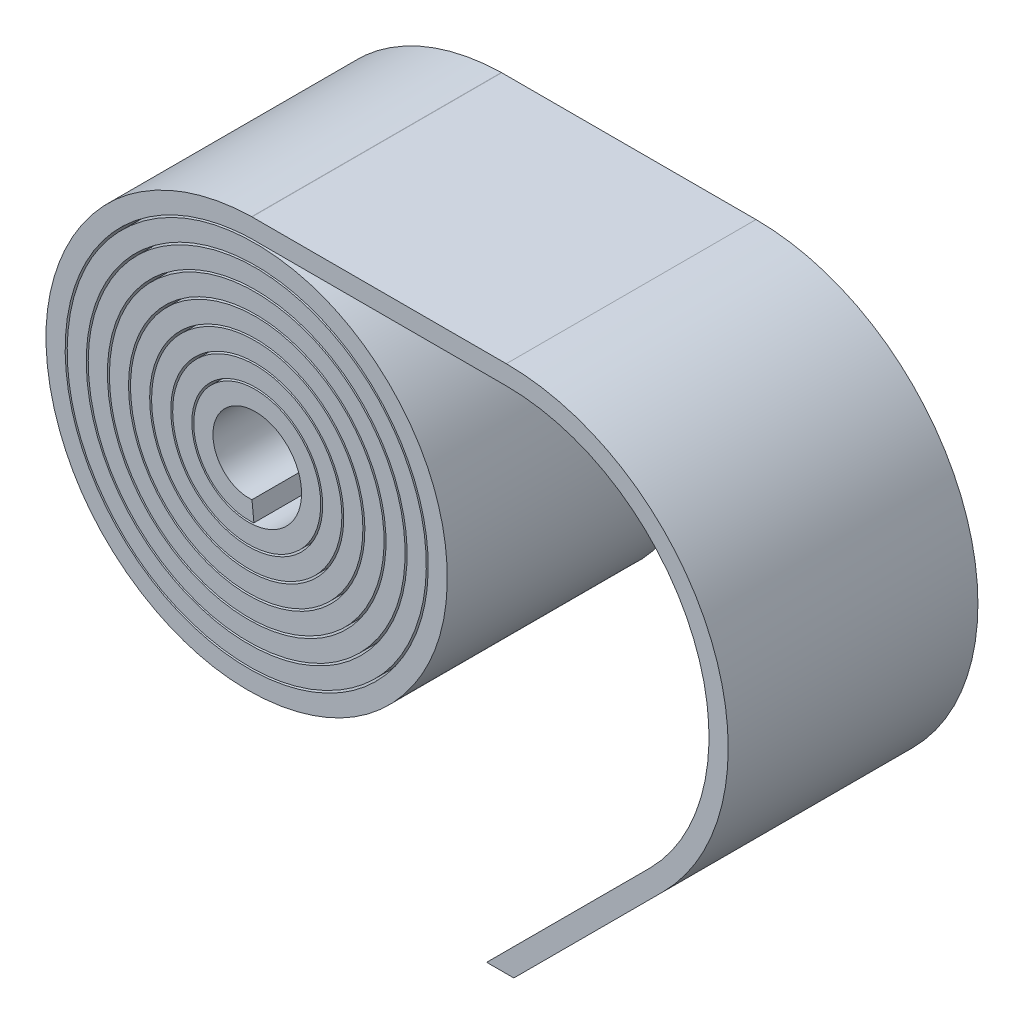
SolidWorks part; units mm, degrees
ref_plane "Front Plane" through (0, 0, 0) normal (0, 0, 1) x (1, 0, 0)
ref_plane "Top Plane" through (0, 0, 0) normal (0, 1, 0) x (1, 0, 0)
ref_plane "Right Plane" through (0, 0, 0) normal (1, 0, 0) x (0, 0, -1)
sketch "Sketch1" plane through (0, 0, 0) normal (0, 0, 1) x (1, 0, 0)
  line L0 (0.3536, 0) -> (-0.3536, 0)
  line L1 (0.3536, 0) -> (4.2426, 3.8891)
  line L4 (4.2426, 3.8891) -> (3.8891, 4.2426)
  line L5 (3.8891, 4.2426) -> (-0.3536, 0)
  point P4 (0, 0)
  dimension "D1" = 45
  dimension "D2" = 0.5
  dimension "D3" = 6
extrude "Boss-Extrude1" add sketch "Sketch1" along normal blind 6.5
sketch "Sketch2" plane through (4.0659, 4.0659, 0) normal (0.7071, 0.7071, 0) x (0, 0, -1)
  line L4 (0, -0.25) -> (0, 0.25)
  line L5 (0, 0.25) -> (-6.5, 0.25)
  line L6 (-6.5, 0.25) -> (-6.5, -0.25)
  line L7 (-6.5, -0.25) -> (0, -0.25)
  line L8 (0, -0.25) -> (0, 0.25)
  line L9 (0, 0.25) -> (-6.5, 0.25)
  line L10 (-6.5, 0.25) -> (-6.5, -0.25)
  line L11 (-6.5, -0.25) -> (0, -0.25)
  dimension "D1" = 0
ref_plane "Plane1" [suppressed] through (6.1872, 6.1872, 0) normal (0.7071, 0.7071, 0) x (0, 0, -1)
sketch "Sketch3" [suppressed] plane through (6.1872, 6.1872, 0) normal (0.7071, 0.7071, 0) x (0, 0, -1)
  line L0 (-6.5, 0.25) -> (-6.5, -0.2731)
  line L1 (0, 0.25) -> (0, -0.2731)
  line L4 (0, -0.25) -> (0, 0.25)
  line L5 (0, 0.25) -> (-6.5, 0.25)
  line L6 (-6.5, 0.25) -> (-6.5, -0.25)
  line L7 (-6.5, -0.25) -> (0, -0.25)
  line L8 (0, -0.25) -> (0, 0.25) construction
  line L9 (0, 0.25) -> (-6.5, 0.25) construction
  line L10 (-6.5, 0.25) -> (-6.5, -0.25) construction
  line L11 (-6.5, -0.25) -> (0, -0.25) construction
  arc A0 (-6.5, 0.25) -> (0, 0.25) centre (-3.25, 10.5625) ccw
  arc A1 (-6.5, -0.2731) -> (0, -0.2731) centre (-3.25, 10.5625) ccw
  arc A2 (-6.6503, -0.2269) -> (0.1503, -0.2269) centre (-3.25, 10.5625) ccw construction
  dimension "D1" = 0
  dimension "D2" = 0.5
loft "Loft1" [suppressed] add profiles "Sketch2", "Sketch3"
sketch "Sketch4" [suppressed] plane through (7.6014, 7.6014, 0) normal (0.7071, 0.7071, 0) x (0, 0, -1)
  line L2 (-6.5, 0.25) -> (-6.5, -0.2731)
  line L3 (0, -0.2731) -> (0, 0.25)
  line L4 (-6.5, 0.25) -> (-6.5, -0.2731)
  line L5 (0, -0.2731) -> (0, 0.25)
  arc A2 (-6.5, 0.25) -> (0, 0.25) centre (-3.25, 10.5625) ccw
  arc A3 (-6.5, -0.2731) -> (0, -0.2731) centre (-3.25, 10.5625) ccw
  arc A4 (-6.5, 0.25) -> (0, 0.25) centre (-3.25, 10.5625) ccw
  arc A5 (-6.5, -0.2731) -> (0, -0.2731) centre (-3.25, 10.5625) ccw
  dimension "D1" = 0
extrude "Boss-Extrude2" [suppressed] add sketch "Sketch4" along normal blind 62
sketch "Sketch5" [suppressed] plane through (7.6014, 7.6014, 0) normal (0.7071, 0.7071, 0) x (0, 0, -1)
  line L2 (-6.5, 0.25) -> (-6.5, -0.2731)
  line L3 (0, -0.2731) -> (0, 0.25)
  line L4 (-6.5, 0.25) -> (-6.5, -0.2731)
  line L5 (0, -0.2731) -> (0, 0.25)
  arc A2 (-6.5, 0.25) -> (0, 0.25) centre (-3.25, 10.5625) ccw
  arc A3 (-6.5, -0.2731) -> (0, -0.2731) centre (-3.25, 10.5625) ccw
  arc A4 (-6.5, 0.25) -> (0, 0.25) centre (-3.25, 10.5625) ccw
  arc A5 (-6.5, -0.2731) -> (0, -0.2731) centre (-3.25, 10.5625) ccw
  dimension "D1" = 0
extrude "Boss-Extrude3" [suppressed] add sketch "Sketch5" along normal blind 28
sketch "Sketch6" [suppressed] plane through (7.6014, 7.6014, 0) normal (0.7071, 0.7071, 0) x (0, 0, -1)
  line L2 (-6.5, 0.25) -> (-6.5, -0.2731)
  line L3 (0, -0.2731) -> (0, 0.25)
  line L4 (-6.5, 0.25) -> (-6.5, -0.2731)
  line L5 (0, -0.2731) -> (0, 0.25)
  arc A2 (-6.5, 0.25) -> (0, 0.25) centre (-3.25, 10.5625) ccw
  arc A3 (-6.5, -0.2731) -> (0, -0.2731) centre (-3.25, 10.5625) ccw
  arc A4 (-6.5, 0.25) -> (0, 0.25) centre (-3.25, 10.5625) ccw
  arc A5 (-6.5, -0.2731) -> (0, -0.2731) centre (-3.25, 10.5625) ccw
  dimension "D1" = 0
extrude "Boss-Extrude4" [suppressed] add sketch "Sketch6" along normal blind 254
sketch "Sketch7" plane through (0, 0, 0) normal (0, 0, 1) x (1, 0, 0)
  line L4 (-6.4619, 13.25) -> (0.1581, 13.25)
  line L5 (0.1581, 13.75) -> (-6.4619, 13.75)
  line L6 (-6.4619, 13.75) -> (-6.4619, 13.25)
  line L7 (3.8891, 4.2426) -> (4.2426, 3.8891)
  circle A0 centre (-6.4619, 8.25) radius 5 construction
  circle A1 centre (-6.4619, 8.25) radius 5 construction
  arc A4 (3.8891, 4.2426) -> (0.1581, 13.25) centre (0.1581, 7.9736) ccw
  arc A5 (4.2426, 3.8891) -> (0.1581, 13.75) centre (0.1581, 7.9736) ccw
  arc A6 (4.2426, 3.8891) -> (0.1581, 13.75) centre (0.1581, 7.9736) ccw construction
  dimension "D2" = 0.5
  dimension "D1" = 0.5
sketch "Sketch8" [suppressed] plane through (0, 0, 0) normal (0, 0, 1) x (1, 0, 0)
  line L4 (-6.4619, 13.25) -> (0.1581, 13.25)
  line L5 (-6.4619, 13.25) -> (-6.4619, 13.75)
  line L6 (-6.4619, 13.75) -> (0.1581, 13.75)
  line L7 (3.8891, 4.2426) -> (4.2426, 3.8891)
  circle A0 centre (-6.4619, 8.25) radius 5 construction
  circle A1 centre (-6.4619, 8.25) radius 5 construction
  arc A4 (3.8891, 4.2426) -> (0.1581, 13.25) centre (0.1581, 7.9736) ccw
  arc A5 (4.2426, 3.8891) -> (0.1581, 13.75) centre (0.1581, 7.9736) ccw
  arc A6 (4.2426, 3.8891) -> (0.1581, 13.75) centre (0.1581, 7.9736) ccw construction
  arc A7 (3.8891, 4.2426) -> (0.1581, 13.25) centre (0.1581, 7.9736) ccw construction
  dimension "D2" = 0.5
  dimension "D1" = 0.5
sketch "Sketch9" [suppressed] plane through (0, 0, 0) normal (0, 0, 1) x (1, 0, 0)
  line L0 (-6.4619, 13.25) -> (0.1581, 13.25)
  line L1 (-6.4619, 13.25) -> (-6.4619, 13.75)
  line L2 (-6.4619, 13.75) -> (0.1581, 13.75)
  line L3 (3.8891, 4.2426) -> (4.2426, 3.8891)
  circle A0 centre (-6.4619, 8.25) radius 5 construction
  circle A1 centre (-6.4619, 8.25) radius 5 construction
  arc A2 (3.8891, 4.2426) -> (0.1581, 13.25) centre (0.1581, 7.9736) ccw
  arc A3 (4.2426, 3.8891) -> (0.1581, 13.75) centre (0.1581, 7.9736) ccw
  arc A4 (4.2426, 3.8891) -> (0.1581, 13.75) centre (0.1581, 7.9736) ccw construction
  arc A5 (3.8891, 4.2426) -> (0.1581, 13.25) centre (0.1581, 7.9736) ccw construction
  dimension "D2" = 0.5
  dimension "D1" = 0.5
extrude "Boss-Extrude7" add sketch "Sketch7" along normal up to surface (6.5 mm away) up to face at (2.0329, 2.0329, 6.5)
extrude "Boss-Extrude8" [suppressed] add sketch "Sketch8" along normal up to surface (6.5 mm away) up to face at (0.2285, 8.0928, 6.5)
extrude "Boss-Extrude9" [suppressed] add sketch "Sketch9" along normal up to surface (6.5 mm away) up to face at (0.2285, 8.0928, 6.5)
sketch "Sketch12" [suppressed] plane through (0, 0, 0) normal (0, 0, 1) x (1, 0, 0)
  circle A0 centre (-6.4619, 8.25) radius 5 construction
  circle A1 centre (-6.4619, 8.25) radius 5
curve "Helix/Spiral1" [suppressed]
sketch "Sketch13" [suppressed] plane through (0, 0, 0) normal (0, 0, 1) x (1, 0, 0)
  line L0 (-6.4707, 13.7499) -> (-6.4619, 13.75)
  line L1 (-6.4619, 13.75) -> (-6.4619, 13.25)
  line L3 (-10.7744, 8.25) -> (-11.2743, 8.2399)
  spline S0 degree 3 poles (-1734.9987, -985.3553) (109.5244, -102.0758) (10.9503, 23.6304) (-9.5072, 12.2267) (-10.113, 11.6566) (-10.9826, 10.3036) (-11.2457, 9.522) (-11.3734, 7.9329) (-11.2381, 7.1267) (-10.607, 5.678) (-10.1119, 5.0367) (-8.8833, 4.0654) (-8.1509, 3.7363) (-6.6233, 3.4616) (-5.8295, 3.5162) (-4.3662, 3.99) (-3.6981, 4.4087) (-2.6409, 5.5064) (-2.2527, 6.1843) (-1.8419, 7.6373) (-1.8195, 8.411) (-2.1394, 9.8723) (-2.4812, 10.5586) (-3.4433, 11.6857) (-4.0625, 12.1255) (-5.4292, 12.6606) (-6.1755, 12.7555) (-7.6191, 12.5845) (-8.3151, 12.3189) (-9.496, 11.4954) (-9.9798, 10.9384) (-19.7569, -8.2721) (108.4322, -92.6781) (765.8503, 1847.6945) knots -1.679483 -1.679483 -1.679483 -1.679483 0.0625 0.0625 0.125 0.125 0.1875 0.1875 0.25 0.25 0.3125 0.3125 0.375 0.375 0.4375 0.4375 0.5 0.5 0.5625 0.5625 0.625 0.625 0.6875 0.6875 0.75 0.75 0.8125 0.8125 0.875 0.875 0.9375 0.9375 2.765017 2.765017 2.765017 2.765017 only from (-6.4619, 13.25) to (-10.7744, 8.25) construction
  spline S1 degree 3 poles (-6.4619, 13.25) (-7.2801, 13.2357) (-8.0901, 13.0167) (-9.5072, 12.2267) (-10.113, 11.6566) (-10.9826, 10.3036) (-11.2457, 9.522) (-11.3734, 7.9329) (-11.2381, 7.1267) (-10.607, 5.678) (-10.1119, 5.0367) (-8.8833, 4.0654) (-8.1509, 3.7363) (-6.6233, 3.4616) (-5.8295, 3.5162) (-4.3662, 3.99) (-3.6981, 4.4087) (-2.6409, 5.5064) (-2.2527, 6.1843) (-1.8419, 7.6373) (-1.8195, 8.411) (-2.1394, 9.8723) (-2.4812, 10.5586) (-3.4433, 11.6857) (-4.0625, 12.1255) (-5.4292, 12.6606) (-6.1755, 12.7555) (-7.6191, 12.5845) (-8.3151, 12.3189) (-9.496, 11.4954) (-9.9798, 10.9384) (-10.6264, 9.6679) (-10.7888, 8.9556) (-10.7744, 8.25) knots 0 0 0 0 0.0625 0.0625 0.125 0.125 0.1875 0.1875 0.25 0.25 0.3125 0.3125 0.375 0.375 0.4375 0.4375 0.5 0.5 0.5625 0.5625 0.625 0.625 0.6875 0.6875 0.75 0.75 0.8125 0.8125 0.875 0.875 0.9375 0.9375 1 1 1 1
  spline S2 degree 1 poles (-6.4707, 13.7499) (-11.2743, 8.2399) knots 0 0 1 1 construction
  spline S3 degree 3 poles (-6.4707, 13.7499) (-7.3581, 13.7344) (-9.1599, 13.2519) (-11.1557, 11.3673) (-12.0281, 8.7814) (-11.5796, 6.112) (-9.9392, 3.9865) (-7.5099, 2.8947) (-4.8746, 3.0758) (-2.6545, 4.4667) (-1.3634, 6.7214) (-1.2888, 9.2966) (-2.4276, 11.5834) (-4.4925, 13.0502) (-6.9836, 13.3674) (-9.3095, 12.4794) (-10.9279, 10.6188) (-11.2902, 9.0229) (-11.2743, 8.2399) knots 0 0 0 0 0.0625 0.125 0.1875 0.25 0.3125 0.375 0.4375 0.5 0.5625 0.625 0.6875 0.75 0.8125 0.875 0.9375 1 1 1 1
  dimension "D1" = 0.5
extrude "Boss-Extrude10" [suppressed] add sketch "Sketch13" along normal up to surface (6.5 mm away) up to face at (0.2285, 8.0928, 6.5)
sketch "Sketch14" [suppressed] plane through (0, 0, 0) normal (0, 0, 1) x (1, 0, 0)
  line L0 (0.1581, 13.25) -> (-6.4619, 13.25) construction
  line L1 (-6.4619, 13.75) -> (-15.4619, 13.75)
  line L2 (-6.4619, 13.75) -> (-6.4619, 13.25)
  line L3 (-6.4619, 13.25) -> (-15.4619, 13.25)
  line L4 (-15.4619, 13.75) -> (-15.4619, 13.25)
  dimension "D1" = 9
extrude "Boss-Extrude11" [suppressed] add sketch "Sketch14" along normal up to surface (6.5 mm away) up to face at (0.2285, 8.0928, 6.5)
sketch "Sketch15" plane through (0, 0, 0) normal (0, 0, 1) x (1, 0, 0)
  circle A0 centre (-6.4619, 8.25) radius 5 construction
  circle A1 centre (-6.4619, 8.25) radius 5
curve "Helix/Spiral2"
sketch "Sketch16" plane through (0, 0, 0) normal (0, 0, 1) x (1, 0, 0)
  line L0 (-6.4707, 13.7499) -> (-6.4619, 13.75)
  line L1 (-6.4619, 13.75) -> (-6.4619, 13.25)
  line L4 (-6.4619, 7.375) -> (-6.4122, 6.8775)
  spline S0 degree 3 poles (-2722.3964, -1245.4042) (118.5986, -153.8828) (15.5928, 22.5679) (-8.8147, 12.6555) (-9.3349, 12.3217) (-10.218, 11.4923) (-10.5808, 10.9969) (-11.1027, 9.9123) (-11.2617, 9.3234) (-11.3575, 8.1315) (-11.2943, 7.5289) (-10.9568, 6.39) (-10.6827, 5.8541) (-9.9627, 4.9193) (-9.517, 4.5207) (-8.5155, 3.9119) (-7.96, 3.7019) (-6.8142, 3.4959) (-6.2244, 3.5) (-5.0891, 3.7188) (-4.544, 3.9334) (-3.5703, 4.5421) (-3.1419, 4.9359) (-2.4574, 5.848) (-2.2014, 6.366) (-1.8932, 7.4557) (-1.8412, 8.0271) (-1.9454, 9.1469) (-2.1015, 9.6948) (-2.5982, 10.6949) (-2.9387, 11.1467) (-3.7564, 11.8955) (-4.2333, 12.1924) (-5.2584, 12.5937) (-5.8062, 12.6981) (-6.8991, 12.7035) (-7.4439, 12.6044) (-8.458, 12.2187) (-8.9272, 11.9322) (-9.7286, 11.2126) (-10.0606, 10.7796) (-10.5456, 9.8267) (-10.6984, 9.3071) (-10.807, 8.2513) (-10.7627, 7.7156) (-10.486, 6.6992) (-10.2536, 6.2189) (-9.6341, 5.3766) (-9.2473, 5.015) (-8.3729, 4.4565) (-7.8855, 4.2599) (-6.8764, 4.0553) (-6.3549, 4.0474) (-5.3476, 4.2185) (-4.862, 4.3975) (-3.9907, 4.9158) (-3.6051, 5.2549) (-2.9837, 6.046) (-2.748, 6.4977) (-2.4554, 7.4518) (-2.3986, 7.9541) (-2.4686, 8.9417) (-2.5954, 9.4268) (-3.013, 10.3159) (-3.3036, 10.7195) (-4.0076, 11.3931) (-4.4207, 11.6629) (-5.3127, 12.0348) (-5.7913, 12.1368) (-6.7494, 12.1624) (-7.2287, 12.0859) (-8.1244, 11.7674) (-8.5405, 11.5255) (-9.2554, 10.911) (-9.5539, 10.5386) (-9.9959, 9.7149) (-10.1391, 9.2638) (-10.2538, 8.3441) (-10.2253, 7.8757) (-10.003, 6.984) (-9.8094, 6.561) (-9.2855, 5.8156) (-8.9555, 5.4935) (-8.2049, 4.9912) (-7.7847, 4.8111) (-6.9113, 4.6145) (-6.4584, 4.598) (-5.5806, 4.7279) (-5.156, 4.8742) (-4.3908, 5.3076) (-4.0504, 5.5945) (-3.4976, 6.2682) (-3.2853, 6.6549) (-3.0147, 7.475) (-2.9564, 7.9082) (-2.9989, 8.7629) (-3.0996, 9.1841) (-3.4438, 9.9588) (-3.6871, 10.3122) (-4.2816, 10.9055) (-4.6326, 11.1452) (-5.3936, 11.4814) (-5.8035, 11.5778) (-6.6266, 11.6169) (-7.0397, 11.5598) (-7.8142, 11.3024) (-8.1754, 11.1022) (-8.7992, 10.5882) (-9.0615, 10.2745) (-9.4544, 9.5772) (-9.5848, 9.1939) (-9.6991, 8.4097) (-9.6829, 8.0091) (-9.5088, 7.2441) (-9.351, 6.88) (-8.9175, 6.2356) (-8.642, 5.9555) (-8.012, 5.515) (-7.6577, 5.3547) (-6.919, 5.1725) (-6.5348, 5.1508) (-5.7879, 5.2459) (-5.4255, 5.3628) (-4.77, 5.7168) (-4.4771, 5.9538) (-3.9982, 6.5142) (-3.8123, 6.8373) (-3.5701, 7.5251) (-3.5137, 7.8895) (-3.5352, 8.6105) (-3.613, 8.9668) (-3.8897, 9.6244) (-4.0884, 9.9254) (-4.5779, 10.4334) (-4.8684, 10.6403) (-5.5009, 10.9346) (-5.8426, 11.022) (-6.5307, 11.0682) (-6.8769, 11.027) (-7.5279, 10.8246) (-7.8325, 10.6633) (-8.3607, 10.2449) (-8.5841, 9.9878) (-8.9221, 9.414) (-9.0365, 9.0974) (-9.1438, 8.4482) (-9.1366, 8.1157) (-9.0043, 7.4791) (-8.8793, 7.1753) (-8.5309, 6.6357) (-8.3076, 6.4002) (-7.7946, 6.0271) (-7.5051, 5.8896) (-6.8997, 5.7285) (-6.5841, 5.7048) (-5.9692, 5.7717) (-5.6701, 5.8622) (-5.1277, 6.1426) (-4.8844, 6.3323) (-4.4847, 6.7833) (-4.3282, 7.0445) (-4.1206, 7.6019) (-4.0695, 7.8979) (-4.0766, 8.4848) (-4.1347, 8.7754) (-4.3499, 9.313) (-4.5068, 9.5597) (-4.8958, 9.9778) (-5.1278, 10.149) (-5.6343, 10.3954) (-5.9085, 10.4704) (-6.4619, 10.517) (-6.7408, 10.4886) (-7.2661, 10.3349) (-7.5124, 10.2096) (-7.9408, 9.8817) (-8.1227, 9.6791) (-8.3999, 9.2255) (-8.4951, 8.9747) (-8.5888, 8.4595) (-8.5873, 8.1952) (-8.4904, 7.6886) (-8.3951, 7.4464) (-8.1263, 7.0155) (-7.9529, 6.8269) (-7.5532, 6.5267) (-7.327, 6.4151) (-6.8535, 6.2813) (-6.6063, 6.2591) (-6.1242, 6.3043) (-5.8895, 6.3716) (-5.4633, 6.584) (-5.2718, 6.7291) (-4.9562, 7.0751) (-4.8321, 7.276) (-4.6653, 7.7052) (-4.6227, 7.9333) (-4.622, 8.3859) (-4.6638, 8.6101) (-4.8236, 9.0251) (-4.9414, 9.2157) (-5.2347, 9.5393) (-5.4101, 9.6722) (-5.7934, 9.8646) (-6.0011, 9.9241) (-6.4201, 9.9646) (-6.6313, 9.9455) (-7.0291, 9.8342) (-7.2155, 9.7419) (-7.54, 9.4993) (-7.6779, 9.349) (-7.8888, 9.0123) (-7.9616, 8.826) (-8.0353, 8.4437) (-8.036, 8.2477) (-7.9681, 7.8724) (-7.8994, 7.6931) (-7.7047, 7.3743) (-7.5786, 7.2349) (-7.2882, 7.0127) (-7.1239, 6.93) (-6.7804, 6.8299) (-6.6013, 6.8126) (-6.2527, 6.8426) (-6.0833, 6.89) (-5.7762, 7.0405) (-5.6386, 7.1435) (-5.4119, 7.3889) (-5.323, 7.5313) (-5.2032, 7.8347) (-5.1725, 7.9957) (-5.1705, 8.314) (-5.1993, 8.4712) (-5.365, 8.9064) (-5.5833, 9.1443) (-6.1095, 9.4096) (-6.4144, 9.4364) (-6.9514, 9.2857) (-7.1811, 9.1098) (-7.459, 8.663) (-7.5065, 8.3947) (-7.4155, 7.9085) (-7.2781, 7.6928) (-0.2208, 2.4009) (69.3767, 103.8125) (-2946.9328, 592.1902) knots -0.321915 -0.321915 -0.321915 -0.321915 0.007812 0.007812 0.015625 0.015625 0.023437 0.023437 0.03125 0.03125 0.039062 0.039062 0.046875 0.046875 0.054687 0.054687 0.0625 0.0625 0.070312 0.070312 0.078125 0.078125 0.085937 0.085937 0.09375 0.09375 0.101562 0.101562 0.109375 0.109375 0.117187 0.117187 0.125 0.125 0.132812 0.132812 0.140625 0.140625 0.148437 0.148437 0.15625 0.15625 0.164062 0.164062 0.171875 0.171875 0.179687 0.179687 0.1875 0.1875 0.195312 0.195312 0.203125 0.203125 0.210938 0.210938 0.21875 0.21875 0.226563 0.226563 0.234375 0.234375 0.242188 0.242188 0.25 0.25 0.257813 0.257813 0.265625 0.265625 0.273438 0.273438 0.28125 0.28125 0.289063 0.289063 0.296875 0.296875 0.304688 0.304688 0.3125 0.3125 0.320313 0.320313 0.328125 0.328125 0.335938 0.335938 0.34375 0.34375 0.351563 0.351563 0.359375 0.359375 0.367188 0.367188 0.375 0.375 0.382813 0.382813 0.390625 0.390625 0.398438 0.398438 0.40625 0.40625 0.414063 0.414063 0.421875 0.421875 0.429688 0.429688 0.4375 0.4375 0.445313 0.445313 0.453125 0.453125 0.460938 0.460938 0.46875 0.46875 0.476563 0.476563 0.484375 0.484375 0.492188 0.492188 0.5 0.5 0.507813 0.507813 0.515625 0.515625 0.523438 0.523438 0.53125 0.53125 0.539063 0.539063 0.546875 0.546875 0.554688 0.554688 0.5625 0.5625 0.570313 0.570313 0.578125 0.578125 0.585938 0.585938 0.59375 0.59375 0.601563 0.601563 0.609375 0.609375 0.617188 0.617188 0.625 0.625 0.632813 0.632813 0.640625 0.640625 0.648438 0.648438 0.65625 0.65625 0.664063 0.664063 0.671875 0.671875 0.679688 0.679688 0.6875 0.6875 0.695313 0.695313 0.703125 0.703125 0.710938 0.710938 0.71875 0.71875 0.726563 0.726563 0.734375 0.734375 0.742188 0.742188 0.75 0.75 0.757813 0.757813 0.765625 0.765625 0.773438 0.773438 0.78125 0.78125 0.789063 0.789063 0.796875 0.796875 0.804688 0.804688 0.8125 0.8125 0.820313 0.820313 0.828125 0.828125 0.835938 0.835938 0.84375 0.84375 0.851563 0.851563 0.859375 0.859375 0.867188 0.867188 0.875 0.875 0.882813 0.882813 0.890625 0.890625 0.898438 0.898438 0.90625 0.90625 0.921875 0.921875 0.9375 0.9375 0.953125 0.953125 0.96875 0.96875 0.984375 0.984375 1.563928 1.563928 1.563928 1.563928 only from (-6.4619, 13.25) to (-6.4619, 7.375) construction
  spline S1 degree 3 poles (-6.4619, 13.25) (-7.0755, 13.2393) (-7.6849, 13.1143) (-8.8147, 12.6555) (-9.3349, 12.3217) (-10.218, 11.4923) (-10.5808, 10.9969) (-11.1027, 9.9123) (-11.2617, 9.3234) (-11.3575, 8.1315) (-11.2943, 7.5289) (-10.9568, 6.39) (-10.6827, 5.8541) (-9.9627, 4.9193) (-9.517, 4.5207) (-8.5155, 3.9119) (-7.96, 3.7019) (-6.8142, 3.4959) (-6.2244, 3.5) (-5.0891, 3.7188) (-4.544, 3.9334) (-3.5703, 4.5421) (-3.1419, 4.9359) (-2.4574, 5.848) (-2.2014, 6.366) (-1.8932, 7.4557) (-1.8412, 8.0271) (-1.9454, 9.1469) (-2.1015, 9.6948) (-2.5982, 10.6949) (-2.9387, 11.1467) (-3.7564, 11.8955) (-4.2333, 12.1924) (-5.2584, 12.5937) (-5.8062, 12.6981) (-6.8991, 12.7035) (-7.4439, 12.6044) (-8.458, 12.2187) (-8.9272, 11.9322) (-9.7286, 11.2126) (-10.0606, 10.7796) (-10.5456, 9.8267) (-10.6984, 9.3071) (-10.807, 8.2513) (-10.7627, 7.7156) (-10.486, 6.6992) (-10.2536, 6.2189) (-9.6341, 5.3766) (-9.2473, 5.015) (-8.3729, 4.4565) (-7.8855, 4.2599) (-6.8764, 4.0553) (-6.3549, 4.0474) (-5.3476, 4.2185) (-4.862, 4.3975) (-3.9907, 4.9158) (-3.6051, 5.2549) (-2.9837, 6.046) (-2.748, 6.4977) (-2.4554, 7.4518) (-2.3986, 7.9541) (-2.4686, 8.9417) (-2.5954, 9.4268) (-3.013, 10.3159) (-3.3036, 10.7195) (-4.0076, 11.3931) (-4.4207, 11.6629) (-5.3127, 12.0348) (-5.7913, 12.1368) (-6.7494, 12.1624) (-7.2287, 12.0859) (-8.1244, 11.7674) (-8.5405, 11.5255) (-9.2554, 10.911) (-9.5539, 10.5386) (-9.9959, 9.7149) (-10.1391, 9.2638) (-10.2538, 8.3441) (-10.2253, 7.8757) (-10.003, 6.984) (-9.8094, 6.561) (-9.2855, 5.8156) (-8.9555, 5.4935) (-8.2049, 4.9912) (-7.7847, 4.8111) (-6.9113, 4.6145) (-6.4584, 4.598) (-5.5806, 4.7279) (-5.156, 4.8742) (-4.3908, 5.3076) (-4.0504, 5.5945) (-3.4976, 6.2682) (-3.2853, 6.6549) (-3.0147, 7.475) (-2.9564, 7.9082) (-2.9989, 8.7629) (-3.0996, 9.1841) (-3.4438, 9.9588) (-3.6871, 10.3122) (-4.2816, 10.9055) (-4.6326, 11.1452) (-5.3936, 11.4814) (-5.8035, 11.5778) (-6.6266, 11.6169) (-7.0397, 11.5598) (-7.8142, 11.3024) (-8.1754, 11.1022) (-8.7992, 10.5882) (-9.0615, 10.2745) (-9.4544, 9.5772) (-9.5848, 9.1939) (-9.6991, 8.4097) (-9.6829, 8.0091) (-9.5088, 7.2441) (-9.351, 6.88) (-8.9175, 6.2356) (-8.642, 5.9555) (-8.012, 5.515) (-7.6577, 5.3547) (-6.919, 5.1725) (-6.5348, 5.1508) (-5.7879, 5.2459) (-5.4255, 5.3628) (-4.77, 5.7168) (-4.4771, 5.9538) (-3.9982, 6.5142) (-3.8123, 6.8373) (-3.5701, 7.5251) (-3.5137, 7.8895) (-3.5352, 8.6105) (-3.613, 8.9668) (-3.8897, 9.6244) (-4.0884, 9.9254) (-4.5779, 10.4334) (-4.8684, 10.6403) (-5.5009, 10.9346) (-5.8426, 11.022) (-6.5307, 11.0682) (-6.8769, 11.027) (-7.5279, 10.8246) (-7.8325, 10.6633) (-8.3607, 10.2449) (-8.5841, 9.9878) (-8.9221, 9.414) (-9.0365, 9.0974) (-9.1438, 8.4482) (-9.1366, 8.1157) (-9.0043, 7.4791) (-8.8793, 7.1753) (-8.5309, 6.6357) (-8.3076, 6.4002) (-7.7946, 6.0271) (-7.5051, 5.8896) (-6.8997, 5.7285) (-6.5841, 5.7048) (-5.9692, 5.7717) (-5.6701, 5.8622) (-5.1277, 6.1426) (-4.8844, 6.3323) (-4.4847, 6.7833) (-4.3282, 7.0445) (-4.1206, 7.6019) (-4.0695, 7.8979) (-4.0766, 8.4848) (-4.1347, 8.7754) (-4.3499, 9.313) (-4.5068, 9.5597) (-4.8958, 9.9778) (-5.1278, 10.149) (-5.6343, 10.3954) (-5.9085, 10.4704) (-6.4619, 10.517) (-6.7408, 10.4886) (-7.2661, 10.3349) (-7.5124, 10.2096) (-7.9408, 9.8817) (-8.1227, 9.6791) (-8.3999, 9.2255) (-8.4951, 8.9747) (-8.5888, 8.4595) (-8.5873, 8.1952) (-8.4904, 7.6886) (-8.3951, 7.4464) (-8.1263, 7.0155) (-7.9529, 6.8269) (-7.5532, 6.5267) (-7.327, 6.4151) (-6.8535, 6.2813) (-6.6063, 6.2591) (-6.1242, 6.3043) (-5.8895, 6.3716) (-5.4633, 6.584) (-5.2718, 6.7291) (-4.9562, 7.0751) (-4.8321, 7.276) (-4.6653, 7.7052) (-4.6227, 7.9333) (-4.622, 8.3859) (-4.6638, 8.6101) (-4.8236, 9.0251) (-4.9414, 9.2157) (-5.2347, 9.5393) (-5.4101, 9.6722) (-5.7934, 9.8646) (-6.0011, 9.9241) (-6.4201, 9.9646) (-6.6313, 9.9455) (-7.0291, 9.8342) (-7.2155, 9.7419) (-7.54, 9.4993) (-7.6779, 9.349) (-7.8888, 9.0123) (-7.9616, 8.826) (-8.0353, 8.4437) (-8.036, 8.2477) (-7.9681, 7.8724) (-7.8994, 7.6931) (-7.7047, 7.3743) (-7.5786, 7.2349) (-7.2882, 7.0127) (-7.1239, 6.93) (-6.7804, 6.8299) (-6.6013, 6.8126) (-6.2527, 6.8426) (-6.0833, 6.89) (-5.7762, 7.0405) (-5.6386, 7.1435) (-5.4119, 7.3889) (-5.323, 7.5313) (-5.2032, 7.8347) (-5.1725, 7.9957) (-5.1705, 8.314) (-5.1993, 8.4712) (-5.365, 8.9064) (-5.5833, 9.1443) (-6.1095, 9.4096) (-6.4144, 9.4364) (-6.9514, 9.2857) (-7.1811, 9.1098) (-7.459, 8.663) (-7.5065, 8.3947) (-7.4155, 7.9085) (-7.2781, 7.6928) (-6.9076, 7.415) (-6.6767, 7.3535) (-6.4619, 7.375) knots 0 0 0 0 0.007812 0.007812 0.015625 0.015625 0.023437 0.023437 0.03125 0.03125 0.039062 0.039062 0.046875 0.046875 0.054687 0.054687 0.0625 0.0625 0.070312 0.070312 0.078125 0.078125 0.085937 0.085937 0.09375 0.09375 0.101562 0.101562 0.109375 0.109375 0.117187 0.117187 0.125 0.125 0.132812 0.132812 0.140625 0.140625 0.148437 0.148437 0.15625 0.15625 0.164062 0.164062 0.171875 0.171875 0.179687 0.179687 0.1875 0.1875 0.195312 0.195312 0.203125 0.203125 0.210938 0.210938 0.21875 0.21875 0.226563 0.226563 0.234375 0.234375 0.242188 0.242188 0.25 0.25 0.257813 0.257813 0.265625 0.265625 0.273438 0.273438 0.28125 0.28125 0.289063 0.289063 0.296875 0.296875 0.304688 0.304688 0.3125 0.3125 0.320313 0.320313 0.328125 0.328125 0.335938 0.335938 0.34375 0.34375 0.351563 0.351563 0.359375 0.359375 0.367188 0.367188 0.375 0.375 0.382813 0.382813 0.390625 0.390625 0.398438 0.398438 0.40625 0.40625 0.414063 0.414063 0.421875 0.421875 0.429688 0.429688 0.4375 0.4375 0.445313 0.445313 0.453125 0.453125 0.460938 0.460938 0.46875 0.46875 0.476563 0.476563 0.484375 0.484375 0.492188 0.492188 0.5 0.5 0.507813 0.507813 0.515625 0.515625 0.523438 0.523438 0.53125 0.53125 0.539063 0.539063 0.546875 0.546875 0.554688 0.554688 0.5625 0.5625 0.570313 0.570313 0.578125 0.578125 0.585938 0.585938 0.59375 0.59375 0.601563 0.601563 0.609375 0.609375 0.617188 0.617188 0.625 0.625 0.632813 0.632813 0.640625 0.640625 0.648438 0.648438 0.65625 0.65625 0.664063 0.664063 0.671875 0.671875 0.679688 0.679688 0.6875 0.6875 0.695313 0.695313 0.703125 0.703125 0.710938 0.710938 0.71875 0.71875 0.726563 0.726563 0.734375 0.734375 0.742188 0.742188 0.75 0.75 0.757813 0.757813 0.765625 0.765625 0.773438 0.773438 0.78125 0.78125 0.789063 0.789063 0.796875 0.796875 0.804688 0.804688 0.8125 0.8125 0.820313 0.820313 0.828125 0.828125 0.835938 0.835938 0.84375 0.84375 0.851563 0.851563 0.859375 0.859375 0.867188 0.867188 0.875 0.875 0.882813 0.882813 0.890625 0.890625 0.898438 0.898438 0.90625 0.90625 0.921875 0.921875 0.9375 0.9375 0.953125 0.953125 0.96875 0.96875 0.984375 0.984375 1 1 1 1
  spline S2 degree 1 poles (-6.4707, 13.7499) (-6.4122, 6.8775) knots 0 0 1 1 construction
  spline S3 degree 3 poles (-6.4707, 13.7499) (-7.1399, 13.7382) (-8.4887, 13.4627) (-10.7802, 11.9953) (-12.3161, 8.8008) (-11.1105, 4.7678) (-7.5545, 2.6174) (-3.5249, 3.4034) (-1.0984, 6.6519) (-1.4784, 10.6378) (-4.4001, 13.3008) (-8.3025, 13.3106) (-11.1621, 10.7302) (-11.5416, 6.9483) (-9.3122, 3.9327) (-5.6847, 3.2068) (-2.5537, 5.0801) (-1.5078, 8.5226) (-3.0242, 11.7292) (-6.2549, 13.0661) (-9.4983, 11.9029) (-11.0951, 8.907) (-10.2773, 5.6644) (-7.5351, 3.8403) (-4.3288, 4.3243) (-2.3114, 6.7977) (-2.4766, 9.9345) (-4.6706, 12.1109) (-7.7073, 12.2461) (-10.0079, 10.3381) (-10.4224, 7.4293) (-8.803, 5.0387) (-6.0466, 4.3687) (-3.5997, 5.7007) (-2.6997, 8.2836) (-3.7494, 10.7543) (-6.1412, 11.857) (-8.6049, 11.0812) (-9.8819, 8.8944) (-9.368, 6.4667) (-7.3967, 5.0444) (-5.0315, 5.3111) (-3.4934, 7.0605) (-3.5302, 9.3389) (-5.0547, 10.9637) (-7.2251, 11.1372) (-8.908, 9.837) (-9.2703, 7.7929) (-8.1905, 6.0795) (-6.2878, 5.5514) (-4.5699, 6.4179) (-3.9002, 8.1675) (-4.5635, 9.8652) (-6.1513, 10.652) (-7.8066, 10.1791) (-8.6855, 8.758) (-8.3878, 7.1653) (-7.1354, 6.2189) (-5.6226, 6.3586) (-4.633, 7.4439) (-4.6336, 8.8623) (-5.5564, 9.872) (-6.8687, 9.9902) (-7.8767, 9.2221) (-8.0924, 8.0243) (-7.4683, 7.0381) (-6.7501, 6.8437) (-6.4122, 6.8775) knots 0 0 0 0 0.007812 0.015625 0.03125 0.046875 0.0625 0.078125 0.09375 0.109375 0.125 0.140625 0.15625 0.171875 0.1875 0.203125 0.21875 0.234375 0.25 0.265625 0.28125 0.296875 0.3125 0.328125 0.34375 0.359375 0.375 0.390625 0.40625 0.421875 0.4375 0.453125 0.46875 0.484375 0.5 0.515625 0.53125 0.546875 0.5625 0.578125 0.59375 0.609375 0.625 0.640625 0.65625 0.671875 0.6875 0.703125 0.71875 0.734375 0.75 0.765625 0.78125 0.796875 0.8125 0.828125 0.84375 0.859375 0.875 0.890625 0.90625 0.921875 0.9375 0.953125 0.96875 0.984375 1 1 1 1
  dimension "D1" = 0.5
extrude "Boss-Extrude12" add sketch "Sketch16" along normal up to surface (6.5 mm away) up to face at (0.2285, 8.0928, 6.5)
